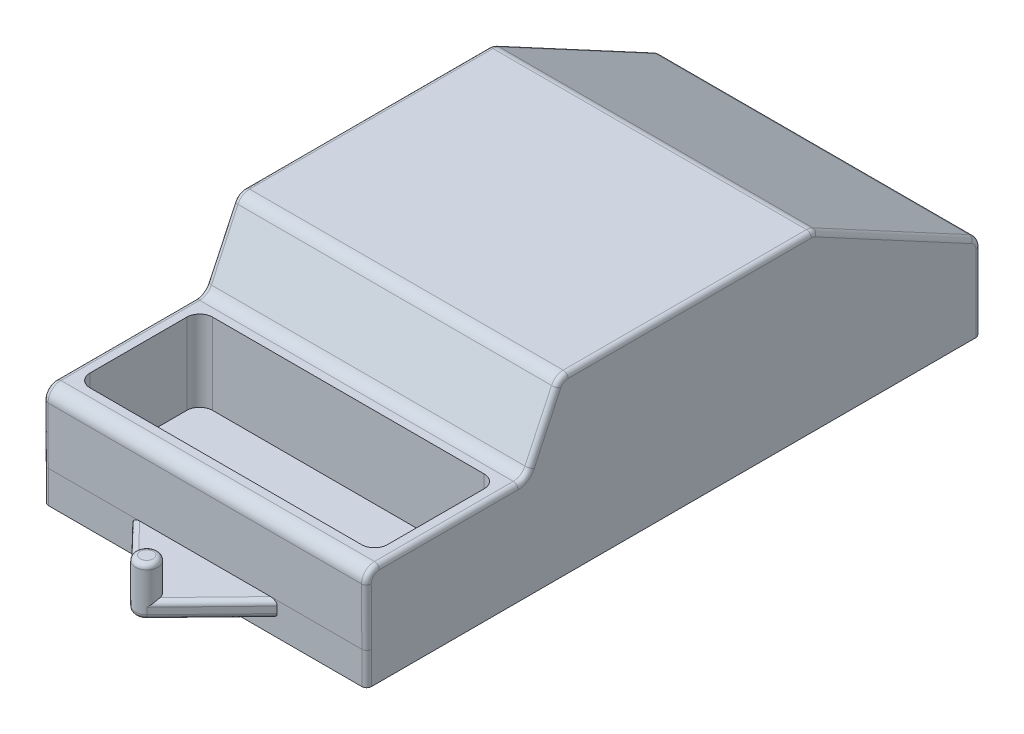
SolidWorks part; units mm, degrees
ref_plane "Front Plane" through (0, 0, 0) normal (0, 0, 1) x (1, 0, 0)
ref_plane "Top Plane" through (0, 0, 0) normal (0, 1, 0) x (1, 0, 0)
ref_plane "Right Plane" through (0, 0, 0) normal (1, 0, 0) x (0, 0, -1)
sketch "Sketch1" plane through (0, 0, 0) normal (0, 1, 0) x (1, 0, 0)
  line L0 (0.1257, -482.6) -> (0.1257, 466.9034) construction
  line L1 (-253.8743, 482.6) -> (254.1257, 482.6)
  line L2 (-253.8743, 482.6) -> (-253.8743, -482.6)
  line L3 (-253.8743, -482.6) -> (254.1257, -482.6)
  line L4 (254.1257, 482.6) -> (254.1257, -482.6)
  circle A0 centre (-177.6743, 279.4) radius 25.4
  circle A1 centre (-177.6978, -228.6) radius 25.4
  circle A2 centre (177.9493, -228.6) radius 25.4
  circle A3 centre (177.9257, 279.4) radius 25.4
  point P0 (0, 0)
  dimension "D3" = 50.8
  dimension "D4" = 50.8
  dimension "D1" = 965.2
  dimension "D2" = 508
  dimension "D5" = 508
  dimension "D6" = 76.2
  dimension "D7" = 203.2
extrude "Boss-Extrude1" add sketch "Sketch1" along normal blind 50.8
ref_plane "Plane1" through (0, 25.4, 0) normal (0, 1, 0) x (1, 0, 0)
sketch "Sketch2" plane through (0, 25.4, 0) normal (0, 1, 0) x (1, 0, 0)
  line L0 (0.1257, -482.6) -> (0.1257, -599.8265) construction
  line L1 (-253.8743, -482.6) -> (254.1257, -482.6) construction
  line L2 (12.9032, -586.6216) -> (113.5578, -482.6)
  line L3 (-12.6517, -586.6216) -> (-113.3064, -482.6)
  line L4 (-113.3064, -482.6) -> (113.5578, -482.6)
  arc A0 (-12.6517, -586.6216) -> (12.9032, -586.6216) centre (0.1257, -574.2577) ccw
  dimension "D1" = 17.78
extrude "Boss-Extrude2" add sketch "Sketch2" along normal blind 25.4
sketch "Sketch4" plane through (0, 50.8, 0) normal (0, 1, 0) x (1, 0, 0)
  circle A1 centre (0.1257, -574.2577) radius 17.78
  arc A2 (-12.6517, -586.6216) -> (12.9032, -586.6216) centre (0.1257, -574.2577) ccw construction
extrude "Boss-Extrude3" add sketch "Sketch4" along normal blind 50.8
fillet "Fillet2" radius 7.62 6 edges at (-62.9791, 25.4, 534.6108) (0.1257, 25.4, 592.0377) (63.2305, 25.4, 534.6108) (63.2305, 50.8, 534.6108) (-62.9791, 50.8, 534.6108) (0.1257, 101.6, 592.0377)
sketch "Sketch7" plane through (-253.8743, 0, 0) normal (-1, 0, 0) x (0, 0, 1)
  line L0 (-482.6, 50.8) -> (-482.6, 120.0143)
  line L1 (-471.8987, 137.9135) -> (-225.884, 270.1169)
  line L2 (-216.2653, 272.5377) -> (166.1252, 272.5377)
  line L3 (184.5154, 260.8609) -> (226.2492, 172.0641)
  line L4 (244.6394, 160.3873) -> (462.7186, 160.3873)
  line L5 (483.0384, 139.9674) -> (482.6, 50.8)
  line L6 (482.6, 50.8) -> (-482.6, 50.8)
  arc A0 (462.7186, 160.3873) -> (483.0384, 139.9674) centre (462.7186, 140.0673) cw
  arc A1 (166.1252, 272.5377) -> (184.5154, 260.8609) centre (166.1252, 252.2177) cw
  arc A2 (-225.884, 270.1169) -> (-216.2653, 272.5377) centre (-216.2653, 252.2177) cw
  arc A3 (-482.6, 120.0143) -> (-471.8987, 137.9135) centre (-462.28, 120.0143) cw
  arc A4 (226.2492, 172.0641) -> (244.6394, 160.3873) centre (244.6394, 180.7073) ccw
  dimension "D1" = 20.32
extrude "Boss-Extrude4" add sketch "Sketch7" against normal blind 508
fillet "Fillet3" radius 7.62 26 edges at (254.1257, 25.4, 482.6) (254.1257, 95.3837, 482.8192) (254.1257, 154.4003, 477.1223) (254.1257, 160.3873, 353.679) (254.1257, 163.5531, 233.7474) (254.1257, 216.4625, 205.3823) (254.1257, 269.3719, 177.0172) (254.1257, 272.5377, -25.07) (254.1257, 271.9232, -221.2246) (254.1257, 204.0152, -348.8913) (254.1257, 130.4414, -479.7207) (254.1257, 60.0071, -482.6) (0.1257, 0, -482.6) (-253.8743, 60.0071, -482.6) (-253.8743, 130.4414, -479.7207) (-253.8743, 204.0152, -348.8913) (-253.8743, 271.9232, -221.2246) (-253.8743, 272.5377, -25.07) (-253.8743, 269.3719, 177.0172) (-253.8743, 216.4625, 205.3823) (-253.8743, 163.5531, 233.7474) (-253.8743, 160.3873, 353.679) (-253.8743, 154.4003, 477.1223) (-253.8743, 95.3837, 482.8192) (-253.8743, 25.4, 482.6) (-253.8743, 0, 0)
sketch "Sketch8" plane through (0, 160.3873, 0) normal (0, 1, 0) x (1, 0, 0)
  line L9 (-233.5543, -450.0186) -> (233.8057, -450.0186)
  line L10 (233.8057, -450.0186) -> (233.8057, -257.3394)
  line L11 (233.8057, -257.3394) -> (-233.5543, -257.3394)
  line L12 (-233.5543, -257.3394) -> (-233.5543, -450.0186)
  line L13 (-213.2343, -450.0186) -> (213.4857, -450.0186)
  line L14 (233.8057, -429.6986) -> (233.8057, -277.6594)
  line L15 (213.4857, -257.3394) -> (-213.2343, -257.3394)
  line L16 (-233.5543, -277.6594) -> (-233.5543, -429.6986)
  arc A0 (-233.5543, -429.6986) -> (-213.2343, -450.0186) centre (-213.2343, -429.6986) ccw
  arc A1 (233.8057, -429.6986) -> (213.4857, -450.0186) centre (213.4857, -429.6986) cw
  arc A2 (213.4857, -257.3394) -> (233.8057, -277.6594) centre (213.4857, -277.6594) cw
  arc A3 (-213.2343, -257.3394) -> (-233.5543, -277.6594) centre (-213.2343, -277.6594) ccw
  dimension "D2" = 20.32
  dimension "D1" = 12.7
extrude "Cut-Extrude1" cut sketch "Sketch8" against normal blind 127
